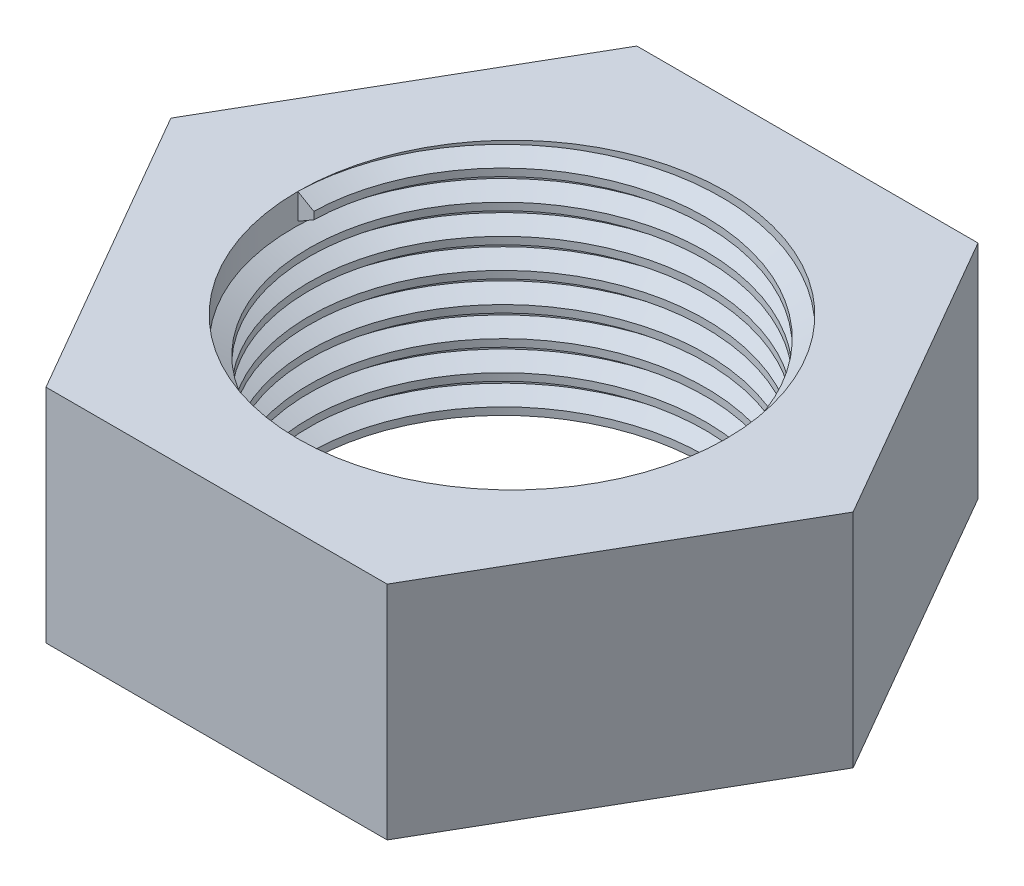
SolidWorks part; units mm, degrees
ref_plane "Front Plane" through (0, 0, 0) normal (0, 0, 1) x (1, 0, 0)
ref_plane "Top Plane" through (0, 0, 0) normal (0, 1, 0) x (1, 0, 0)
ref_plane "Right Plane" through (0, 0, 0) normal (1, 0, 0) x (0, 0, -1)
sketch "Sketch2" plane through (0, 0, 0) normal (0, 1, 0) x (1, 0, 0)
  line L1 (23.094, 0) -> (11.547, 20)
  line L2 (11.547, 20) -> (-11.547, 20)
  line L3 (-11.547, 20) -> (-23.094, 0)
  line L4 (-23.094, 0) -> (-11.547, -20)
  line L5 (-11.547, -20) -> (11.547, -20)
  line L6 (11.547, -20) -> (23.094, 0)
  circle A0 centre (0, 0) radius 20 construction
extrude "Boss-Extrude1" add sketch "Sketch2" along normal blind 15
sketch "Sketch3" plane through (0, 15, 0) normal (0, 1, 0) x (1, 0, 0)
  circle A0 centre (0, 0) radius 14.5
  dimension "D1" = 29
extrude "Cut-Extrude1" cut sketch "Sketch3" against normal through all
thread "Thread3" pitch 2 method extrude profile "Thread Profile3" start angle 0, offset 0, length 15, pitch 2, diameter 29
ref_plane "Plane3" through (-14.5, 15, 0) normal (0, 0, 1) x (-1, 0, 0)
sketch "Thread Profile3" plane through (-14.5, 15, 0) normal (0, 0, 1) x (-1, 0, 0)
  line L0 (0, 0) -> (0, 2) construction
  line L11 (0, 0) -> (0, 1.75)
  line L12 (0, 1.75) -> (-1.0825, 1.125)
  line L13 (-1.0825, 1.125) -> (-1.0825, 0.625)
  line L15 (-1.0825, 0.625) -> (0, 0)
  line L17 (-1.0825, 0.875) -> (0, 0.875) construction
  point P2 (0, 0)
  dimension "Pitch" = 2
  dimension "Profile_Angle" = 60
  dimension "Profile_Land" = 0.5
  dimension "Profile_Height" = 1.0825
